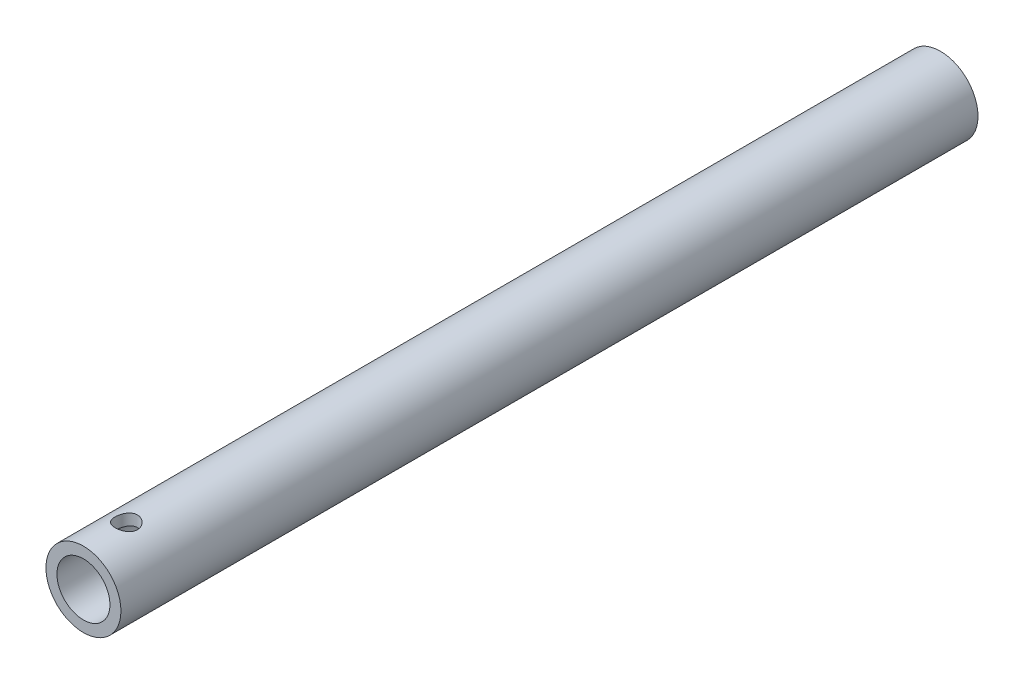
SolidWorks part; units mm, degrees
ref_plane "Front Plane" through (0, 0, 0) normal (0, 0, 1) x (1, 0, 0)
ref_plane "Top Plane" through (0, 0, 0) normal (0, 1, 0) x (1, 0, 0)
ref_plane "Right Plane" through (0, 0, 0) normal (1, 0, 0) x (0, 0, -1)
sketch "Sketch1" plane through (0, 0, 0) normal (0, 0, 1) x (1, 0, 0)
  circle A0 centre (0, 0) radius 13.335
  dimension "Pipe OD" = 26.67
extrude "Extrude-Thin1" add sketch "Sketch1" along normal mid plane 304.8 thin thin type one direction reverse wall 3.9116
sketch "Sketch2" plane through (0, 0, 0) normal (0, 1, 0) x (1, 0, 0)
  line L0 (-13.335, -152.4) -> (13.335, -152.4) construction
  line L1 (0, -137.16) -> (0, 0) construction
  circle A0 centre (0, -137.16) radius 3.9687
  dimension "D1" = 7.9375
  dimension "D2" = 15.24
extrude "Cut-Extrude1" cut sketch "Sketch2" against normal through all both and the other way through all
